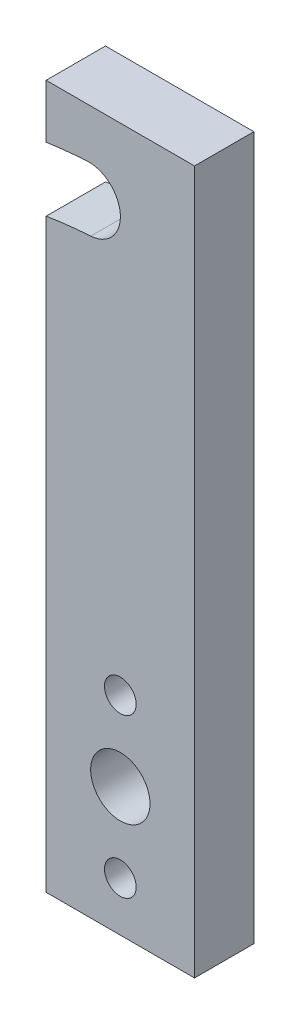
SolidWorks part; units mm, degrees
ref_plane "Plano frontal" through (0, 0, 0) normal (0, 0, 1) x (1, 0, 0)
ref_plane "Plano superior" through (0, 0, 0) normal (0, 1, 0) x (1, 0, 0)
ref_plane "Plano direito" through (0, 0, 0) normal (1, 0, 0) x (0, 0, -1)
sketch "Esboço1" plane through (0, 0, 0) normal (0, 0, 1) x (1, 0, 0)
  line L0 (0, -14.5457) -> (0, -30.5457) construction
  line L1 (-7.5, -35.5457) -> (7.5, -35.5457)
  line L2 (-7.5, -35.5457) -> (-7.5, 35.5457)
  line L3 (-7.5, 35.5457) -> (7.5, 35.5457)
  line L4 (7.5, -35.5457) -> (7.5, 35.5457)
  line L5 (-7.5, -35.5457) -> (7.5, 35.5457) construction
  line L6 (-7.5, 35.5457) -> (7.5, -35.5457) construction
  circle A0 centre (0, -30.5457) radius 1.6
  circle A1 centre (0, -14.5457) radius 1.6
  circle A2 centre (0, -22.5457) radius 3
  arc A3 (-3.1935, 27.3522) -> (-8.0128, 26.8081) centre (0, -22.5457) ccw construction
  arc A4 (-3.3978, 30.5457) -> (-8.5256, 29.9667) centre (0, -22.5457) ccw
  arc A5 (-2.9891, 24.1588) -> (-7.5, 23.6494) centre (0, -22.5457) ccw
  arc A6 (-2.9891, 24.1588) -> (-3.3978, 30.5457) centre (-3.1935, 27.3522) ccw
  arc A7 (-8.5256, 29.9667) -> (-7.5, 23.6494) centre (-8.0128, 26.8081) ccw
  point P0 (0, 0)
  point P14 (-5.6097, 27.1386)
  point P20 (0, 27.5566)
  point P21 (0, 35.5457)
  dimension "D1" = 6
  dimension "D2" = 3.2
  dimension "D4" = 16
  dimension "D6" = 3.2
  dimension "D3" = 15
  dimension "D5" = 5
  dimension "D7" = 5
  dimension "D8" = 50
extrude "Ressalto-extrusão1" add sketch "Esboço1" along normal blind 6 contours A6 A5 L2 L1 L4 L3 A4 A2 A1 A0 region at (0.1818, -0.197, 0)
